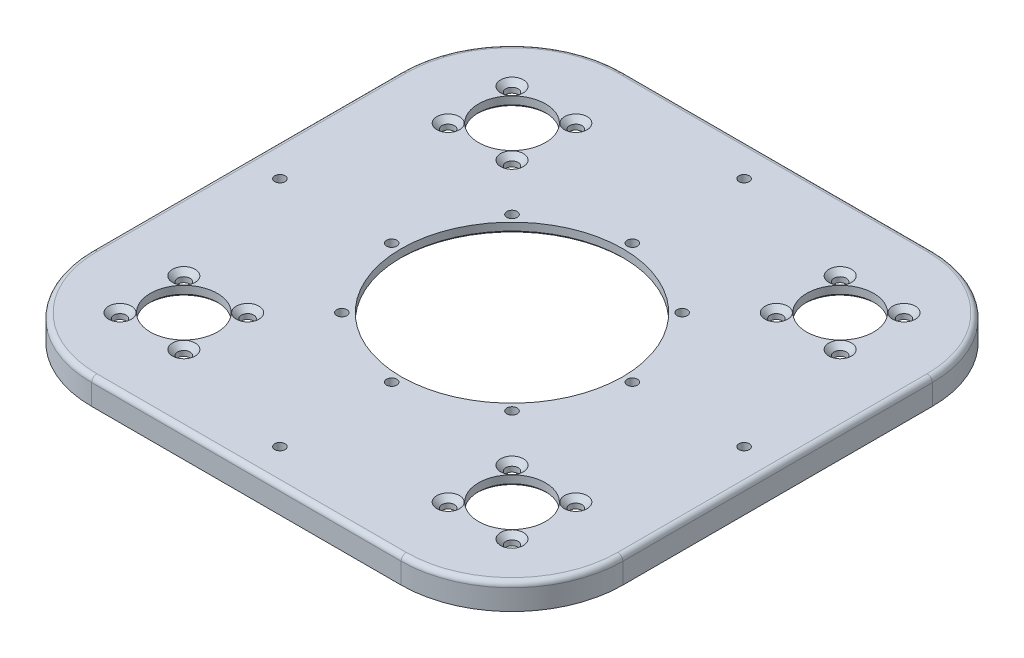
SolidWorks part; units mm, degrees
ref_plane "Спереди" through (0, 0, 0) normal (0, 0, 1) x (1, 0, 0)
ref_plane "Сверху" through (0, 0, 0) normal (0, 1, 0) x (1, 0, 0)
ref_plane "Справа" through (0, 0, 0) normal (1, 0, 0) x (0, 0, -1)
sketch "Эскиз1" plane through (0, 0, 0) normal (0, 1, 0) x (1, 0, 0)
  line L1 (-100, -100) -> (100, -100)
  line L2 (-100, -100) -> (-100, 100)
  line L3 (-100, 100) -> (100, 100)
  line L4 (100, -100) -> (100, 100)
  line L5 (0, 100) -> (0, -100) construction
  line L6 (-100, 0) -> (100, 0) construction
  circle A4 centre (0, 90) radius 2
  circle A5 centre (90, 0) radius 2
  circle A6 centre (0, -90) radius 2
  circle A7 centre (-90, 0) radius 2
  circle A8 centre (0, 46.669) radius 2
  circle A9 centre (33, 33) radius 2
  circle A10 centre (46.669, 0) radius 2
  circle A11 centre (33, -33) radius 2
  circle A12 centre (0, -46.669) radius 2
  circle A13 centre (-33, -33) radius 2
  circle A14 centre (-46.669, 0) radius 2
  circle A15 centre (-33, 33) radius 2
  circle A16 centre (0, 0) radius 43
  point P0 (0, 0)
  point P15 (0, 0)
  point P24 (0, 0)
  point P32 (0, 0)
  dimension "D2" = 4
  dimension "D4" = 90
  dimension "D7" = 86
  dimension "D1" = 200
  dimension "D6" = 46.669
  dimension "D5" = 4
  dimension "D3" = 8
extrude "Бобышка-Вытянуть1" add sketch "Эскиз1" along normal blind 4
fillet "Скругление1" radius 40 4 edges at (100, 2, -100) (-100, 2, -100) (-100, 2, 100) (100, 2, 100)
sketch "Эскиз2" plane through (0, 4, 0) normal (0, 1, 0) x (1, 0, 0)
  line L0 (0, 73.3189) -> (0, 0) construction
  line L1 (0, 0) -> (79.5004, 79.5004) construction
  line L2 (42.8848, 84.3944) -> (81.4162, 45.8631) construction
  line L3 (0, 0) -> (130.6499, 0) construction
  circle A0 centre (63.6396, 63.6396) radius 17.5 construction
  circle A5 centre (63.6396, 63.6396) radius 13
  circle A23 centre (51.2652, 76.014) radius 2.4
  circle A50 centre (76.014, 76.014) radius 2.4
  circle A51 centre (76.014, 51.2652) radius 2.4
  circle A52 centre (51.2652, 51.2652) radius 2.4
  circle A53 centre (63.6396, -63.6396) radius 13
  circle A54 centre (76.014, -51.2652) radius 2.4
  circle A55 centre (51.2652, -51.2652) radius 2.4
  circle A56 centre (51.2652, -76.014) radius 2.4
  circle A57 centre (76.014, -76.014) radius 2.4
  circle A58 centre (-76.014, -76.014) radius 2.4
  circle A59 centre (-51.2652, -76.014) radius 2.4
  circle A60 centre (-51.2652, -51.2652) radius 2.4
  circle A61 centre (-76.014, -51.2652) radius 2.4
  circle A62 centre (-63.6396, -63.6396) radius 13
  circle A63 centre (-63.6396, 63.6396) radius 13
  circle A64 centre (-76.014, 51.2652) radius 2.4
  circle A65 centre (-51.2652, 51.2652) radius 2.4
  circle A66 centre (-51.2652, 76.014) radius 2.4
  circle A67 centre (-76.014, 76.014) radius 2.4
  point P13 (80.6102, 80.6102)
  point P19 (46.669, 46.669)
  point P21 (63.6396, 63.6396)
  point P27 (63.6396, 63.6396)
  point P63 (0, 0)
  dimension "D2" = 45
  dimension "D3" = 4
  dimension "D5" = 26
  dimension "D1" = 90
extrude "Вырез-Вытянуть1" cut sketch "Эскиз2" against normal blind 6
chamfer "Фаска3" distance 2 angle 45 16 edges at (-76.014, 4, -53.6652) (76.014, 4, 73.614) (51.2652, 4, 73.614) (51.2652, 4, 48.8652) (76.014, 4, 48.8652) (-76.014, 4, 78.414) (-51.2652, 4, 78.414) (-76.014, 4, 53.6652) (-51.2652, 4, 53.6652) (-51.2652, 4, -53.6652) (-76.014, 4, -78.414) (-51.2652, 4, -78.414) (51.2652, 4, -48.8652) (76.014, 4, -48.8652) (76.014, 4, -73.614) (51.2652, 4, -73.614)
sketch "Эскиз3" plane through (0, 4, 0) normal (0, 1, 0) x (1, 0, 0)
  line L0 (0, 106.3018) -> (0, 0) construction
  line L1 (0, 0) -> (99.7412, 99.7412) construction
  line L2 (51.2652, 76.014) -> (76.014, 51.2652) construction
  line L3 (75.8808, 40.5255) -> (40.5255, 75.8808) construction
  line L4 (75.8808, 40.5255) -> (87.1945, 51.8392) construction
  line L5 (40.5255, 75.8808) -> (51.8392, 87.1945) construction
  line L6 (87.1945, 51.8392) -> (51.8392, 87.1945) construction
  line L7 (75.8808, 40.5255) -> (51.8392, 87.1945) construction
  line L8 (40.5255, 75.8808) -> (87.1945, 51.8392) construction
  line L9 (40.5255, 75.8808) -> (49.0108, 67.3955)
  line L10 (40.5255, 75.8808) -> (32.0402, 67.3955)
  line L11 (49.0108, 67.3955) -> (40.5255, 58.9103)
  line L12 (32.0402, 67.3955) -> (40.5255, 58.9103)
  line L13 (67.3955, 49.0108) -> (58.9103, 40.5255)
  line L14 (67.3955, 32.0402) -> (58.9103, 40.5255)
  line L15 (75.8808, 40.5255) -> (67.3955, 32.0402)
  line L16 (75.8808, 40.5255) -> (67.3955, 49.0108)
  line L17 (-75.8808, 40.5255) -> (-67.3955, 49.0108)
  line L18 (-75.8808, 40.5255) -> (-67.3955, 32.0402)
  line L19 (-67.3955, 32.0402) -> (-58.9103, 40.5255)
  line L20 (-67.3955, 49.0108) -> (-58.9103, 40.5255)
  line L21 (-49.0108, 67.3955) -> (-40.5255, 58.9103)
  line L22 (-32.0402, 67.3955) -> (-40.5255, 58.9103)
  line L23 (-40.5255, 75.8808) -> (-32.0402, 67.3955)
  line L24 (-40.5255, 75.8808) -> (-49.0108, 67.3955)
  line L25 (0, 0) -> (-122.8864, 0) construction
  line L26 (-40.5255, -75.8808) -> (-49.0108, -67.3955)
  line L27 (-40.5255, -75.8808) -> (-32.0402, -67.3955)
  line L28 (-32.0402, -67.3955) -> (-40.5255, -58.9103)
  line L29 (-49.0108, -67.3955) -> (-40.5255, -58.9103)
  line L30 (-67.3955, -49.0108) -> (-58.9103, -40.5255)
  line L31 (-67.3955, -32.0402) -> (-58.9103, -40.5255)
  line L32 (-75.8808, -40.5255) -> (-67.3955, -32.0402)
  line L33 (-75.8808, -40.5255) -> (-67.3955, -49.0108)
  line L34 (75.8808, -40.5255) -> (67.3955, -49.0108)
  line L35 (75.8808, -40.5255) -> (67.3955, -32.0402)
  line L36 (67.3955, -32.0402) -> (58.9103, -40.5255)
  line L37 (67.3955, -49.0108) -> (58.9103, -40.5255)
  line L38 (49.0108, -67.3955) -> (40.5255, -58.9103)
  line L39 (32.0402, -67.3955) -> (40.5255, -58.9103)
  line L40 (40.5255, -75.8808) -> (32.0402, -67.3955)
  line L41 (40.5255, -75.8808) -> (49.0108, -67.3955)
  point P9 (63.86, 63.86)
  dimension "D1" = 50
  dimension "D2" = 45
  dimension "D3" = 16
  dimension "D4" = 12
extrude "Бобышка-Вытянуть2" [suppressed] add sketch "Эскиз3" along normal blind 14
chamfer "Фаска4" [suppressed] distance 10 angle 45
fillet "Скругление2" [suppressed] radius 2
sketch "Эскиз4" plane through (0, 4, 0) normal (0, -1, 0) x (1, 0, 0)
  line L0 (-100, -60) -> (-100, 60) construction
  line L1 (60, -100) -> (-60, -100) construction
  line L2 (100, 60) -> (100, -60) construction
  line L3 (-60, 100) -> (60, 100) construction
  line L4 (-100, -60) -> (-100, 60)
  line L5 (60, -100) -> (-60, -100)
  line L6 (100, 60) -> (100, -60)
  line L7 (-60, 100) -> (60, 100)
  arc A0 (-60, 100) -> (-100, 60) centre (-60, 60) ccw construction
  arc A1 (-100, -60) -> (-60, -100) centre (-60, -60) ccw construction
  arc A2 (60, -100) -> (100, -60) centre (60, -60) ccw construction
  arc A3 (100, 60) -> (60, 100) centre (60, 60) ccw construction
  arc A4 (-60, 100) -> (-100, 60) centre (-60, 60) ccw
  arc A5 (-100, -60) -> (-60, -100) centre (-60, -60) ccw
  arc A6 (60, -100) -> (100, -60) centre (60, -60) ccw
  arc A7 (100, 60) -> (60, 100) centre (60, 60) ccw
extrude "Вытянуть-Тонкостенный1" add sketch "Эскиз4" along normal blind 10 thin thin type one direction wall 3
fillet "Скругление3" radius 2 8 edges at (90.4056, 4, -90.4056) (0, 4, -103) (-90.4056, 4, -90.4056) (-103, 4, 0) (-90.4056, 4, 90.4056) (0, 4, 103) (90.4056, 4, 90.4056) (103, 4, 0)
chamfer "Фаска5" distance 1 angle 45 5 edges at (0, 0, 43) (63.6396, 0, 50.6396) (-63.6396, 0, 50.6396) (-63.6396, 0, -76.6396) (63.6396, 0, -76.6396)
